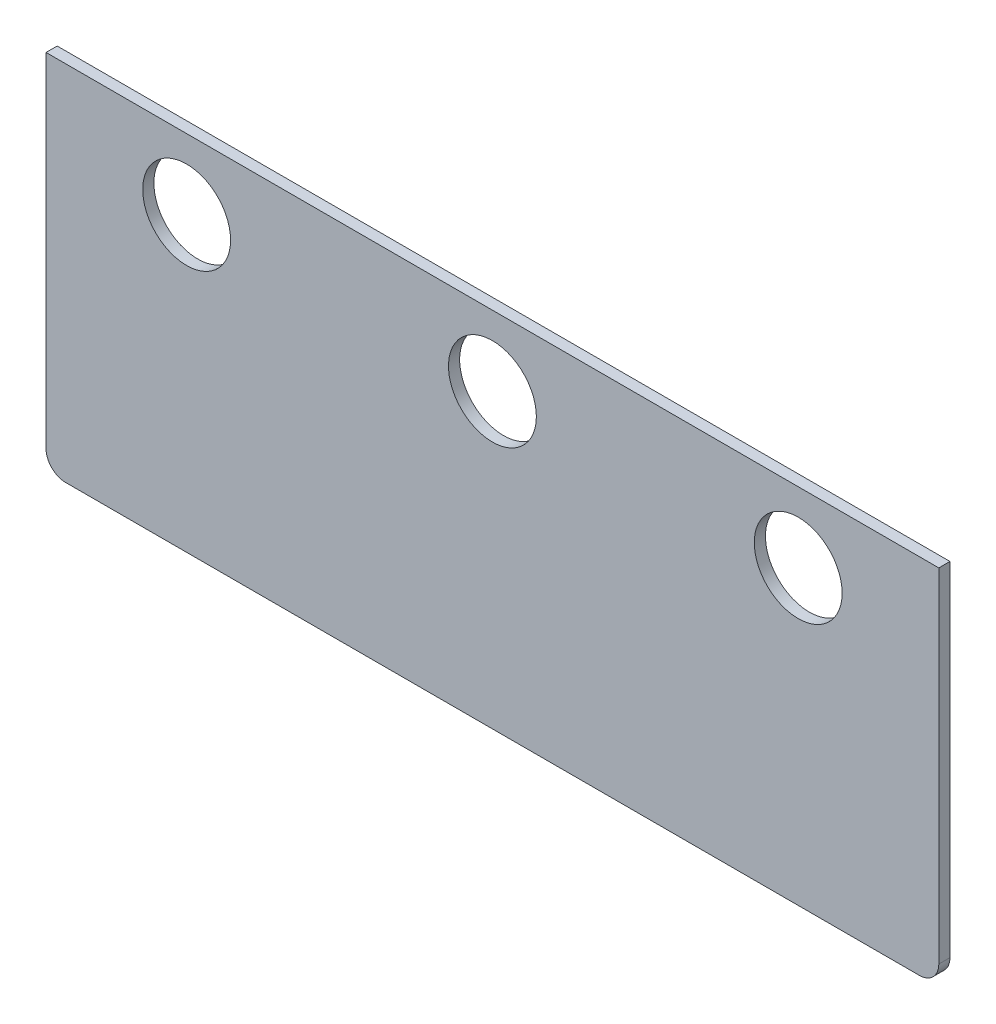
SolidWorks part; units mm, degrees
material "5052-H32"
ref_plane "Front Plane" through (0, 0, 0) normal (0, 0, 1) x (1, 0, 0)
ref_plane "Top Plane" through (0, 0, 0) normal (0, 1, 0) x (1, 0, 0)
ref_plane "Right Plane" through (0, 0, 0) normal (1, 0, 0) x (0, 0, -1)
sketch "Sketch1" plane through (0, 0, 0) normal (0, 0, 1) x (1, 0, 0)
  line L0 (-127, 103.175) -> (-127, 0)
  line L2 (127, 0) -> (127, 103.175)
  line L3 (127, 103.175) -> (-127, 103.175)
  line L4 (-127, 0) -> (127, 0)
  circle A0 centre (87, 83.175) radius 12.5
  circle A1 centre (-87, 83.175) radius 12.5
  circle A2 centre (0, 83.175) radius 12.5
  point P3 (-115.2333, 0)
  point P10 (86.3427, 0)
  point P11 (-128.1212, 0)
  point P12 (0, 103.175)
  point P18 (0, 0)
  dimension "D4" = 25
  dimension "D1" = 103.175
  dimension "D2" = 254
  dimension "D3" = 20
  dimension "D5" = 40
  dimension "D6" = 40
extrude "Boss-Extrude1" add sketch "Sketch1" along normal blind 3.175
fillet "Fillet1" radius 5.5562 2 edges at (127, 0, 1.5875) (-127, 0, 1.5875)
equation "\"L\"= 420mm"
equation "\"W\"= 255mm"
equation "\"H\"= 110mm"
equation "\"Compartment Width\"= 80"
equation "\"T\"= 4.7625 * 2 / 3mm"
equation "\"Inside Fillet Radius\"= 5.55625mm"
equation "\"D1@Boss-Extrude1\"=\"T\""
equation "\"Hole\"=25mm"
equation "\"D4@Sketch1\"=\"Hole\""
equation "\"D2@Sketch1\"=\"W\"-1"
equation "\"D1@Sketch1\"=\"H\"+\"T\"-10"
equation "\"Offset\"= 18mm"
equation "\"Wheel to Wall\"= 43"
equation "\"D1@Fillet1\"=\"Inside Fillet Radius\""
